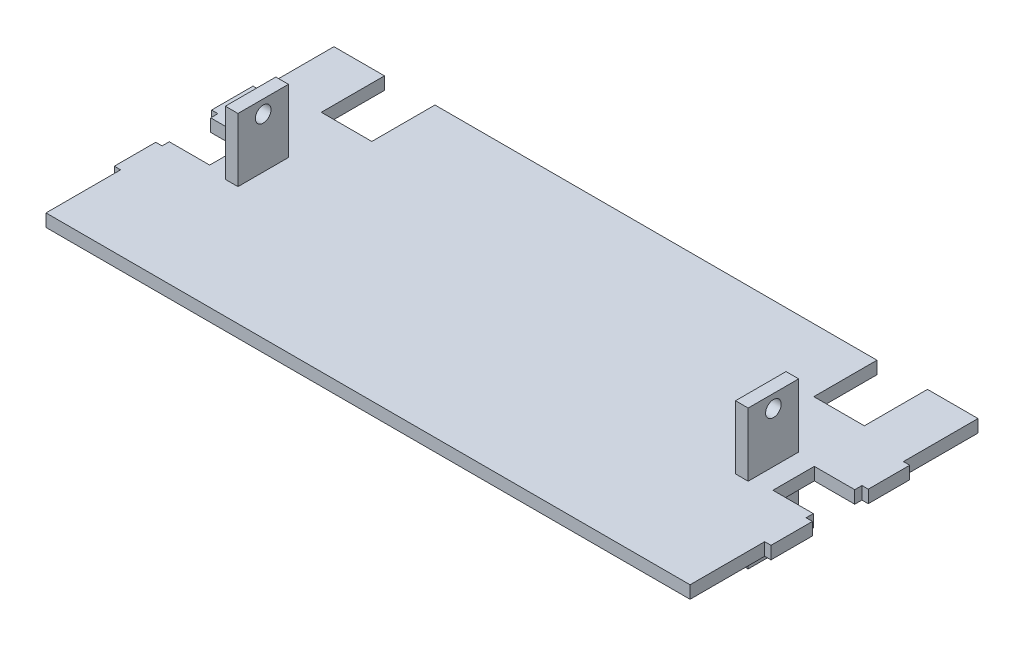
SolidWorks part; units mm, degrees
ref_plane "Front Plane" through (0, 0, 0) normal (0, 0, 1) x (1, 0, 0)
ref_plane "Top Plane" through (0, 0, 0) normal (0, 1, 0) x (1, 0, 0)
ref_plane "Right Plane" through (0, 0, 0) normal (1, 0, 0) x (0, 0, -1)
sketch "Sketch1" plane through (0, 0, 0) normal (0, 1, 0) x (1, 0, 0)
  line L0 (0, 72.39) -> (0, -72.39) construction
  line L1 (161.925, -72.39) -> (-161.925, -72.39)
  line L2 (161.925, -72.39) -> (161.925, -34.8747)
  line L3 (161.925, 72.39) -> (136.525, 72.39)
  line L4 (-161.925, -72.39) -> (-161.925, -34.8747)
  line L5 (161.925, -72.39) -> (-161.925, 72.39) construction
  line L6 (161.925, 72.39) -> (-161.925, -72.39) construction
  line L7 (161.925, 10.414) -> (141.605, 10.414)
  line L9 (161.925, -10.414) -> (141.605, -10.414)
  line L10 (141.605, 10.414) -> (141.605, -10.414)
  line L11 (-136.525, 72.39) -> (-161.925, 72.39)
  line L13 (-161.925, -10.414) -> (-141.605, -10.414)
  line L14 (-141.605, 10.414) -> (-141.605, -10.414)
  line L15 (-161.925, 10.414) -> (-141.605, 10.414)
  line L17 (-127, 0) -> (127, 0) construction
  line L18 (-161.925, 14.0467) -> (-165.1, 14.0467)
  line L20 (-161.925, 34.8747) -> (-165.1, 34.8747)
  line L21 (-165.1, 14.0467) -> (-165.1, 34.8747)
  line L22 (-161.925, -34.8747) -> (-165.1, -34.8747)
  line L23 (-165.1, -14.0467) -> (-165.1, -34.8747)
  line L24 (-161.925, -14.0467) -> (-165.1, -14.0467)
  line L27 (161.925, -14.0467) -> (165.1, -14.0467)
  line L28 (165.1, -14.0467) -> (165.1, -34.8747)
  line L29 (161.925, -34.8747) -> (165.1, -34.8747)
  line L30 (161.925, 34.8747) -> (165.1, 34.8747)
  line L31 (165.1, 14.0467) -> (165.1, 34.8747)
  line L32 (161.925, 14.0467) -> (165.1, 14.0467)
  line L34 (-161.925, 34.8747) -> (-161.925, 72.39)
  line L35 (-161.925, -14.0467) -> (-161.925, -10.414)
  line L36 (161.925, 34.8747) -> (161.925, 72.39)
  line L37 (161.925, -14.0467) -> (161.925, -10.414)
  line L38 (-161.925, 10.414) -> (-161.925, 14.0467)
  line L39 (161.925, 10.414) -> (161.925, 14.0467)
  line L40 (-136.525, 72.39) -> (-136.525, 40.64)
  line L41 (-136.525, 40.64) -> (-111.125, 40.64)
  line L42 (-111.125, 72.39) -> (-111.125, 40.64)
  line L44 (111.125, 72.39) -> (111.125, 40.64)
  line L45 (111.125, 40.64) -> (136.525, 40.64)
  line L46 (136.525, 72.39) -> (136.525, 40.64)
  line L47 (111.125, 72.39) -> (-111.125, 72.39)
  point P0 (0, 0)
  point P6 (127, 0)
  dimension "D1" = 323.85
  dimension "D2" = 144.78
  dimension "D3" = 20.828
  dimension "D5" = 3.175
  dimension "D6" = 20.828
  dimension "D4" = 20.32
  dimension "D7" = 31.75
  dimension "D8" = 25.4
  dimension "D9" = 25.4
  dimension "D10" = 31.75
  dimension "D12" = 25.4
  dimension "D11" = 25.4
extrude "Boss-Extrude1" add sketch "Sketch1" along normal mid plane 6.35
sketch "Sketch2" plane through (0, 0, 0) normal (0, 1, 0) x (1, 0, 0)
  line L0 (-141.605, 10.414) -> (-141.605, -10.414) construction
  line L1 (125.095, -12.7) -> (131.445, -12.7)
  line L2 (125.095, -12.7) -> (125.095, 12.7)
  line L3 (125.095, 12.7) -> (131.445, 12.7)
  line L4 (131.445, -12.7) -> (131.445, 12.7)
  line L5 (125.095, -12.7) -> (131.445, 12.7) construction
  line L6 (125.095, 12.7) -> (131.445, -12.7) construction
  line L9 (-125.095, -12.7) -> (-125.095, 12.7)
  line L10 (-125.095, 12.7) -> (-131.445, 12.7)
  line L11 (-131.445, -12.7) -> (-131.445, 12.7)
  line L12 (-125.095, -12.7) -> (-131.445, -12.7)
  line L13 (141.605, -10.414) -> (141.605, 10.414) construction
  point P0 (128.27, 0)
  point P10 (141.605, 0)
  dimension "D1" = 10.16
  dimension "D2" = 10.16
  dimension "D3" = 25.4
  dimension "D4" = 25.4
  dimension "D5" = 6.35
  dimension "D6" = 6.35
  dimension "D7" = 6.35
extrude "Boss-Extrude2" add sketch "Sketch2" along normal mid plane 70.104
sketch "Sketch3" plane through (-131.445, 0, 0) normal (-1, 0, 0) x (0, 0, 1)
  circle A0 centre (0, 28.4406) radius 3.937
  circle A1 centre (0, -28.4406) radius 3.937
  dimension "D1" = 7.874
  dimension "D2" = 7.874
extrude "Cut-Extrude1" cut sketch "Sketch3" against normal through all both and the other way through all
equation "\"length\"=12.75"
equation "\"width\"= 5.7"
equation "\"height\"= 0.25"
equation "\"D1@Sketch1\"=\"length\""
equation "\"D2@Sketch1\"=\"width\""
equation "\"eyebolt width\"= 0.82"
equation "\"eyebolt length\"= 0.8"
equation "\"D3@Sketch1\"=\"eyebolt width\""
equation "\"D4@Sketch1\"=\"eyebolt length\""
equation "\"lead screw holder height\"= 2.76"
equation "\"lead screw diameter\"= 0.31"
equation "\"D1@Sketch3\"=\"lead screw diameter\""
equation "\"distance from holders to board\"=0.4"
equation "\"D2@Sketch3\"=\"lead screw diameter\""
